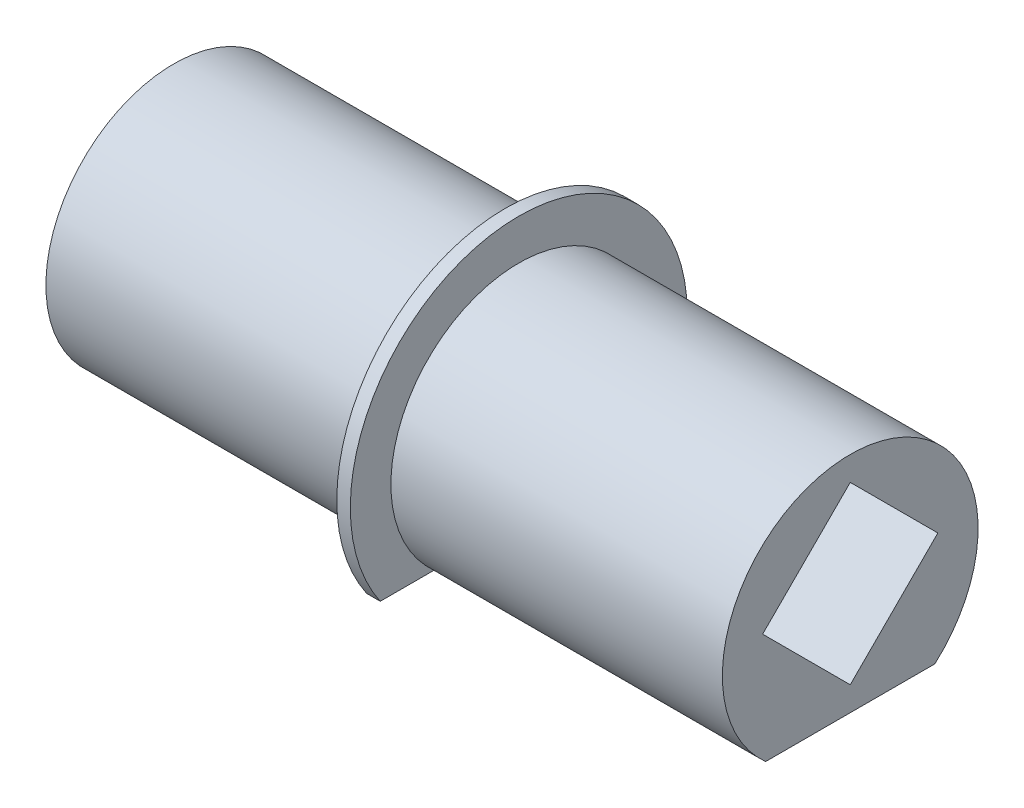
SolidWorks part; units mm, degrees
ref_plane "Plan de face" through (0, 0, 0) normal (0, 0, 1) x (1, 0, 0)
ref_plane "Plan de dessus" through (0, 0, 0) normal (0, 1, 0) x (1, 0, 0)
ref_plane "Plan de droite" through (0, 0, 0) normal (1, 0, 0) x (0, 0, -1)
sketch "Esquisse1" plane through (0, 0, 0) normal (1, 0, 0) x (0, 0, -1)
  line L0 (-6.2523, -7.086) -> (6.2523, -7.086)
  arc A0 (-6.2523, -7.086) -> (6.2523, -7.086) centre (0, 0) cw
  point P4 (0, 0)
  point P5 (0, 0)
  point P6 (0, -7.086)
  dimension "D1" = 9.45
extrude "Boss.-Extru.1" add sketch "Esquisse1" along normal mid plane 50
sketch "Esquisse3" plane through (0, 0, 0) normal (1, 0, 0) x (0, 0, -1)
  line L0 (-10.2368, -7.086) -> (10.2368, -7.086)
  line L1 (-6.2523, -7.086) -> (6.2523, -7.086) construction
  arc A2 (8.2372, -9.3355) -> (-8.2372, -9.3355) centre (0, 0) ccw
  arc A3 (10.2368, -7.086) -> (-10.2368, -7.086) centre (0, 0) ccw
  point P0 (15.9301, -13.5294)
  dimension "D1" = 3
extrude "Boss.-Extru.2" add sketch "Esquisse3" along normal mid plane 1
sketch "Esquisse2" plane through (0, 0, 0) normal (1, 0, 0) x (0, 0, -1)
  line L0 (0, 9.45) -> (0, 7.658) construction
  line L7 (0, -5.2939) -> (0, -7.086) construction
  line L8 (-6.2523, -7.086) -> (6.2523, -7.086) construction
  line L9 (-6.4759, 1.182) -> (0, -5.2939)
  line L16 (-6.4759, 1.182) -> (0, 7.658)
  line L17 (0, -5.2939) -> (6.4759, 1.182)
  line L18 (0, 7.658) -> (6.4759, 1.182)
  line L19 (-6.4759, 1.182) -> (6.4759, 1.182) construction
  line L20 (0, -5.2939) -> (0, 7.658) construction
  arc A1 (6.2523, -7.086) -> (-6.2523, -7.086) centre (0, 0) ccw construction
  point P0 (6.4759, 1.182)
  point P2 (0, 14.831)
  point P13 (11.5559, 2.364)
extrude "Enlèv. mat.-Extru.1" cut sketch "Esquisse2" against normal mid plane 100
